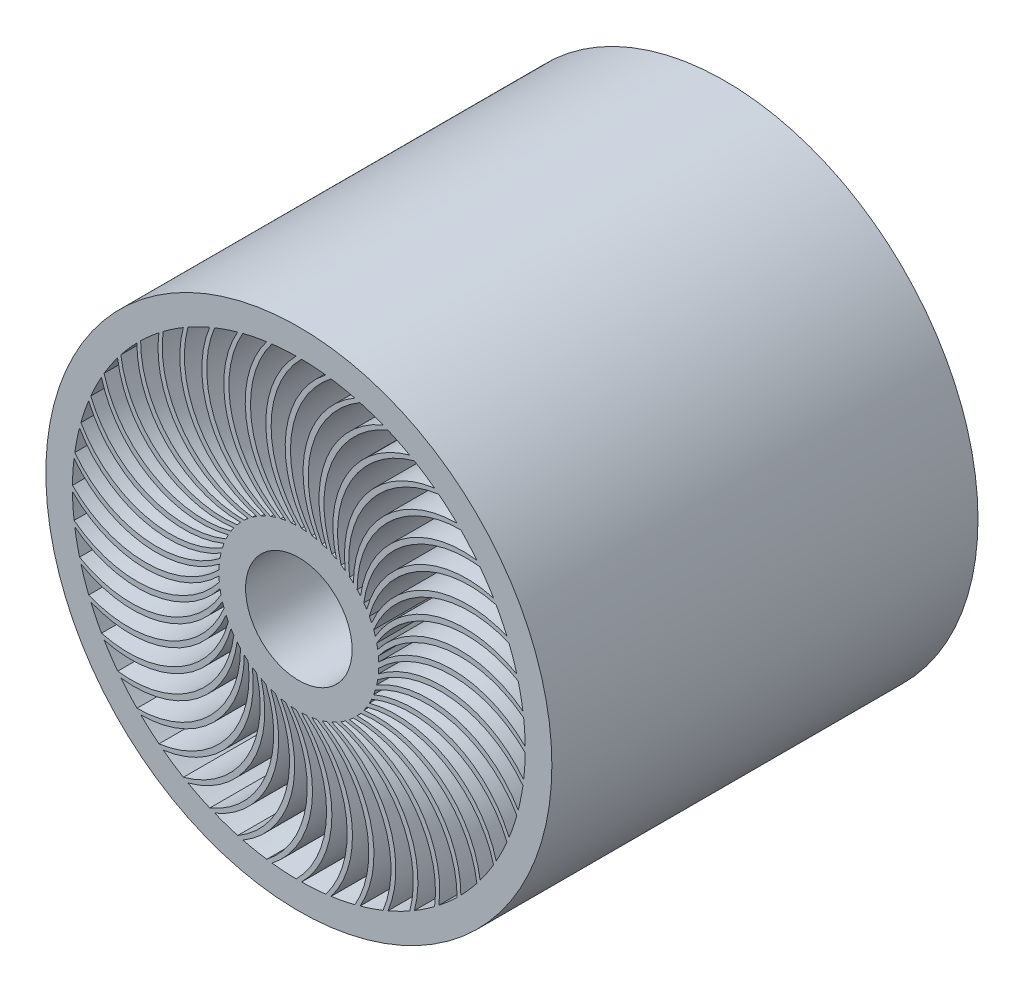
SolidWorks part; units mm, degrees
ref_plane "Front Plane" through (0, 0, 0) normal (0, 0, 1) x (1, 0, 0)
ref_plane "Top Plane" through (0, 0, 0) normal (0, 1, 0) x (1, 0, 0)
ref_plane "Right Plane" through (0, 0, 0) normal (1, 0, 0) x (0, 0, -1)
sketch "Sketch1" plane through (0, 0, 0) normal (0, 0, 1) x (1, 0, 0)
  line L0 (0, 38.1) -> (0, 107.95)
  line L1 (0, 107.95) -> (99.4973, 107.95) construction
  circle A0 centre (0, 0) radius 127
  circle A1 centre (0, 0) radius 120.65
  circle A2 centre (0, 0) radius 107.95
  circle A3 centre (0, 0) radius 25.4
  circle A4 centre (0, 0) radius 38.1
  arc A5 (0, 38.1) -> (0, 107.95) centre (34.925, 73.025) cw
  arc A6 (1.2679, 38.0789) -> (1.2468, 107.95) centre (36.1718, 73.025) cw
  arc A7 (-1.2721, 38.0788) -> (-1.2934, 107.95) centre (33.6317, 73.025) cw
  arc A8 (6.2274, 37.5876) -> (15.3264, 106.8637) centre (45.394, 67.6789) cw
  arc A9 (3.7091, 37.919) -> (12.808, 107.1953) centre (42.8756, 68.0104) cw
  arc A10 (11.0802, 36.4532) -> (29.1438, 103.949) centre (53.8395, 61.1748) cw
  arc A11 (8.6268, 37.1105) -> (26.6902, 104.6064) centre (51.3859, 61.8322) cw
  arc A12 (15.7436, 34.6951) -> (42.4626, 99.2557) centre (61.3638, 53.624) cw
  arc A13 (13.3968, 35.667) -> (40.1158, 100.2277) centre (59.0171, 54.596) cw
  arc A14 (20.1375, 32.3433) -> (55.0548, 92.864) centre (67.8382, 45.1556) cw
  arc A15 (17.9377, 33.6132) -> (52.8549, 94.1341) centre (65.6384, 46.4257) cw
  arc A16 (24.1869, 29.4382) -> (66.7049, 84.8835) centre (73.1518, 35.9146) cw
  arc A17 (22.1717, 30.9843) -> (64.6897, 86.4298) centre (71.1366, 37.461) cw
  arc A18 (27.8224, 26.0293) -> (77.2138, 75.4506) centre (77.2138, 26.0592) cw
  arc A19 (26.0262, 27.8253) -> (75.4176, 77.2467) centre (75.4176, 27.8553) cw
  arc A20 (30.9819, 22.1751) -> (86.4015, 64.7267) centre (79.9546, 15.7578) cw
  arc A21 (29.4355, 24.1901) -> (84.8552, 66.7419) centre (78.4083, 17.773) cw
  arc A22 (33.6112, 17.9414) -> (94.1108, 52.8952) centre (81.3274, 5.1868) cw
  arc A23 (32.3411, 20.141) -> (92.8408, 55.0951) centre (80.0573, 7.3866) cw
  arc A24 (35.6655, 13.4008) -> (100.2099, 40.1588) centre (81.3086, -5.4729) cw
  arc A25 (34.6934, 15.7474) -> (99.2379, 42.5056) centre (80.3366, -3.1261) cw
  arc A26 (37.1095, 8.6308) -> (104.5944, 26.7352) centre (79.8987, -16.039) cw
  arc A27 (36.452, 11.0843) -> (103.937, 29.1888) centre (79.2412, -13.5854) cw
  arc A28 (37.9186, 3.7132) -> (107.1892, 12.8542) centre (77.1216, -26.3307) cw
  arc A29 (37.5869, 6.2315) -> (106.8577, 15.3726) centre (76.7901, -23.8123) cw
  arc A30 (38.0789, -1.2679) -> (107.95, -1.2468) centre (73.025, -36.1718) cw
  arc A31 (38.0788, 1.2721) -> (107.95, 1.2934) centre (73.025, -33.6317) cw
  arc A32 (37.5876, -6.2274) -> (106.8637, -15.3264) centre (67.6789, -45.394) cw
  arc A33 (37.919, -3.7091) -> (107.1953, -12.808) centre (68.0104, -42.8756) cw
  arc A34 (36.4532, -11.0802) -> (103.949, -29.1438) centre (61.1748, -53.8395) cw
  arc A35 (37.1105, -8.6268) -> (104.6064, -26.6902) centre (61.8322, -51.3859) cw
  arc A36 (34.6951, -15.7436) -> (99.2557, -42.4626) centre (53.624, -61.3638) cw
  arc A37 (35.667, -13.3968) -> (100.2277, -40.1158) centre (54.596, -59.0171) cw
  arc A38 (32.3433, -20.1375) -> (92.864, -55.0548) centre (45.1556, -67.8382) cw
  arc A39 (33.6132, -17.9377) -> (94.1341, -52.8549) centre (46.4257, -65.6384) cw
  arc A40 (29.4382, -24.1869) -> (84.8835, -66.7049) centre (35.9146, -73.1518) cw
  arc A41 (30.9843, -22.1717) -> (86.4298, -64.6897) centre (37.461, -71.1366) cw
  arc A42 (26.0293, -27.8224) -> (75.4506, -77.2138) centre (26.0592, -77.2138) cw
  arc A43 (27.8253, -26.0262) -> (77.2467, -75.4176) centre (27.8553, -75.4176) cw
  arc A44 (22.1751, -30.9819) -> (64.7267, -86.4015) centre (15.7578, -79.9546) cw
  arc A45 (24.1901, -29.4355) -> (66.7419, -84.8552) centre (17.773, -78.4083) cw
  arc A46 (17.9414, -33.6112) -> (52.8952, -94.1108) centre (5.1868, -81.3274) cw
  arc A47 (20.141, -32.3411) -> (55.0951, -92.8408) centre (7.3866, -80.0573) cw
  arc A48 (13.4008, -35.6655) -> (40.1588, -100.2099) centre (-5.4729, -81.3086) cw
  arc A49 (15.7474, -34.6934) -> (42.5056, -99.2379) centre (-3.1261, -80.3366) cw
  arc A50 (8.6308, -37.1095) -> (26.7352, -104.5944) centre (-16.039, -79.8987) cw
  arc A51 (11.0843, -36.452) -> (29.1888, -103.937) centre (-13.5854, -79.2412) cw
  arc A52 (3.7132, -37.9186) -> (12.8542, -107.1892) centre (-26.3307, -77.1216) cw
  arc A53 (6.2315, -37.5869) -> (15.3726, -106.8577) centre (-23.8123, -76.7901) cw
  arc A54 (-1.2679, -38.0789) -> (-1.2468, -107.95) centre (-36.1718, -73.025) cw
  arc A55 (1.2721, -38.0788) -> (1.2934, -107.95) centre (-33.6317, -73.025) cw
  arc A56 (-6.2274, -37.5876) -> (-15.3264, -106.8637) centre (-45.394, -67.6789) cw
  arc A57 (-3.7091, -37.919) -> (-12.808, -107.1953) centre (-42.8756, -68.0104) cw
  arc A58 (-11.0802, -36.4532) -> (-29.1438, -103.949) centre (-53.8395, -61.1748) cw
  arc A59 (-8.6268, -37.1105) -> (-26.6902, -104.6064) centre (-51.3859, -61.8322) cw
  arc A60 (-15.7436, -34.6951) -> (-42.4626, -99.2557) centre (-61.3638, -53.624) cw
  arc A61 (-13.3968, -35.667) -> (-40.1158, -100.2277) centre (-59.0171, -54.596) cw
  arc A62 (-20.1375, -32.3433) -> (-55.0548, -92.864) centre (-67.8382, -45.1556) cw
  arc A63 (-17.9377, -33.6132) -> (-52.8549, -94.1341) centre (-65.6384, -46.4257) cw
  arc A64 (-24.1869, -29.4382) -> (-66.7049, -84.8835) centre (-73.1518, -35.9146) cw
  arc A65 (-22.1717, -30.9843) -> (-64.6897, -86.4298) centre (-71.1366, -37.461) cw
  arc A66 (-27.8224, -26.0293) -> (-77.2138, -75.4506) centre (-77.2138, -26.0592) cw
  arc A67 (-26.0262, -27.8253) -> (-75.4176, -77.2467) centre (-75.4176, -27.8553) cw
  arc A68 (-30.9819, -22.1751) -> (-86.4015, -64.7267) centre (-79.9546, -15.7578) cw
  arc A69 (-29.4355, -24.1901) -> (-84.8552, -66.7419) centre (-78.4083, -17.773) cw
  arc A70 (-33.6112, -17.9414) -> (-94.1108, -52.8952) centre (-81.3274, -5.1868) cw
  arc A71 (-32.3411, -20.141) -> (-92.8408, -55.0951) centre (-80.0573, -7.3866) cw
  arc A72 (-35.6655, -13.4008) -> (-100.2099, -40.1588) centre (-81.3086, 5.4729) cw
  arc A73 (-34.6934, -15.7474) -> (-99.2379, -42.5056) centre (-80.3366, 3.1261) cw
  arc A74 (-37.1095, -8.6308) -> (-104.5944, -26.7352) centre (-79.8987, 16.039) cw
  arc A75 (-36.452, -11.0843) -> (-103.937, -29.1888) centre (-79.2412, 13.5854) cw
  arc A76 (-37.9186, -3.7132) -> (-107.1892, -12.8542) centre (-77.1216, 26.3307) cw
  arc A77 (-37.5869, -6.2315) -> (-106.8577, -15.3726) centre (-76.7901, 23.8123) cw
  arc A78 (-38.0789, 1.2679) -> (-107.95, 1.2468) centre (-73.025, 36.1718) cw
  arc A79 (-38.0788, -1.2721) -> (-107.95, -1.2934) centre (-73.025, 33.6317) cw
  arc A80 (-37.5876, 6.2274) -> (-106.8637, 15.3264) centre (-67.6789, 45.394) cw
  arc A81 (-37.919, 3.7091) -> (-107.1953, 12.808) centre (-68.0104, 42.8756) cw
  arc A82 (-36.4532, 11.0802) -> (-103.949, 29.1438) centre (-61.1748, 53.8395) cw
  arc A83 (-37.1105, 8.6268) -> (-104.6064, 26.6902) centre (-61.8322, 51.3859) cw
  arc A84 (-34.6951, 15.7436) -> (-99.2557, 42.4626) centre (-53.624, 61.3638) cw
  arc A85 (-35.667, 13.3968) -> (-100.2277, 40.1158) centre (-54.596, 59.0171) cw
  arc A86 (-32.3433, 20.1375) -> (-92.864, 55.0548) centre (-45.1556, 67.8382) cw
  arc A87 (-33.6132, 17.9377) -> (-94.1341, 52.8549) centre (-46.4257, 65.6384) cw
  arc A88 (-29.4382, 24.1869) -> (-84.8835, 66.7049) centre (-35.9146, 73.1518) cw
  arc A89 (-30.9843, 22.1717) -> (-86.4298, 64.6897) centre (-37.461, 71.1366) cw
  arc A90 (-26.0293, 27.8224) -> (-75.4506, 77.2138) centre (-26.0592, 77.2138) cw
  arc A91 (-27.8253, 26.0262) -> (-77.2467, 75.4176) centre (-27.8553, 75.4176) cw
  arc A92 (-22.1751, 30.9819) -> (-64.7267, 86.4015) centre (-15.7578, 79.9546) cw
  arc A93 (-24.1901, 29.4355) -> (-66.7419, 84.8552) centre (-17.773, 78.4083) cw
  arc A94 (-17.9414, 33.6112) -> (-52.8952, 94.1108) centre (-5.1868, 81.3274) cw
  arc A95 (-20.141, 32.3411) -> (-55.0951, 92.8408) centre (-7.3866, 80.0573) cw
  arc A96 (-13.4008, 35.6655) -> (-40.1588, 100.2099) centre (5.4729, 81.3086) cw
  arc A97 (-15.7474, 34.6934) -> (-42.5056, 99.2379) centre (3.1261, 80.3366) cw
  arc A98 (-8.6308, 37.1095) -> (-26.7352, 104.5944) centre (16.039, 79.8987) cw
  arc A99 (-11.0843, 36.452) -> (-29.1888, 103.937) centre (13.5854, 79.2412) cw
  arc A100 (-3.7132, 37.9186) -> (-12.8542, 107.1892) centre (26.3307, 77.1216) cw
  arc A101 (-6.2315, 37.5869) -> (-15.3726, 106.8577) centre (23.8123, 76.7901) cw
  point P158 (0, 0)
  dimension "D1" = 254
  dimension "D2" = 241.3
  dimension "D3" = 215.9
  dimension "D4" = 50.8
  dimension "D5" = 76.2
  dimension "D6" = 2
  dimension "D9" = 2.54
  dimension "D7" = 2
  dimension "D8" = 48
extrude "Boss-Extrude2" add sketch "Sketch1" along normal blind 203.2 contours A4 | A79 A4 A78 A2 | A81 A4 A80 A2 | A83 A4 A82 A2 | A85 A4 A84 A2 | A87 A4 A86 A2 | A89 A4 A88 A2 | A91 A4 A90 A2 | A93 A4 A92 A2 | A95 A4 A94 A2 | A97 A4 A96 A2 | A99 A4 A98 A2 | A101 A4 A100 A2 | A4 A6 L0 | L0 A6 A5 | A7 A4 A5 A2 | L0 A6 A2 | A9 L0 A8 A2 | A9 L0 A8 | A9 A4 A8 L0 | A11 A4 A10 A2 | A13 A4 A12 A2 | A15 A4 A14 A2 | A17 A4 A16 A2 | A19 A4 A18 A2 | A21 A4 A20 A2 | A23 A4 A22 A2 | A25 A4 A24 A2 | A27 A4 A26 A2 | A29 A4 A28 A2 | A31 A4 A30 A2 | A33 A4 A32 A2 | A35 A4 A34 A2 | A37 A4 A36 A2 | A39 A4 A38 A2 | A41 A4 A40 A2 | A43 A4 A42 A2 | A45 A4 A44 A2 | A47 A4 A46 A2 | A49 A4 A48 A2 | A51 A4 A50 A2 | A53 A4 A52 A2 | A55 A4 A54 A2 | A57 A4 A56 A2 | A59 A4 A58 A2 | A61 A4 A60 A2 | A63 A4 A62 A2 | A65 A4 A64 A2 | A67 A4 A66 A2 | A69 A4 A68 A2 | A71 A4 A70 A2 | A73 A4 A72 A2 | A75 A4 A74 A2 | A77 A4 A76 A2 | A2 L1 A1 A6 | L1 A2 A6 region at (-13.7531, 73.025, 0) region at (0.4188, 38.5237, 0) region at (0.6161, 37.0172, 0) region at (-0.6373, 38.1663, 0) region at (0.4111, 107.52, 0) region at (99.7068, 61.6699, 0) region at (0.9323, 107.9479, 0) region at (-6.0211, 68.0104, 0) region at (2.3373, 41.8954, 0) region at (-5.0704, 38.497, 0) region at (6.0662, 98.5561, 0) region at (4.3808, 74.4062, 0) region at (-10.0529, 37.5098, 0) region at (14.0547, 73.1981, 0) region at (-14.8627, 35.8761, 0) region at (23.4859, 70.739, 0) region at (-19.4166, 33.6263, 0) region at (32.5153, 67.0706, 0) region at (-23.6374, 30.8013, 0) region at (40.9903, 62.254, 0) region at (-27.4543, 27.4512, 0) region at (48.7665, 56.3697, 0) region at (-30.8039, 23.634, 0) region at (55.7089, 49.5189, 0) region at (-33.6285, 19.4129, 0) region at (61.697, 41.8207, 0) region at (-35.8778, 14.8587, 0) region at (66.6281, 33.4092, 0) region at (-37.5109, 10.0488, 0) region at (70.4183, 24.4307, 0) region at (-38.4975, 5.0661, 0) region at (73.0047, 15.0406, 0) region at (-38.8192, -0.0021, 0) region at (-38.497, -5.0704, 0) region at (74.342, 5.3727, 0) region at (-37.5098, -10.0529, 0) region at (74.4062, -4.3808, 0) region at (-35.8761, -14.8627, 0) region at (73.1981, -14.0547, 0) region at (-33.6263, -19.4166, 0) region at (70.739, -23.4859, 0) region at (-30.8013, -23.6374, 0) region at (67.0706, -32.5153, 0) region at (-27.4512, -27.4543, 0) region at (62.254, -40.9903, 0) region at (-23.634, -30.8039, 0) region at (56.3697, -48.7665, 0) region at (-19.4129, -33.6285, 0) region at (49.5189, -55.7089, 0) region at (-14.8587, -35.8778, 0) region at (41.8207, -61.697, 0) region at (-10.0488, -37.5109, 0) region at (33.4092, -66.6281, 0) region at (-5.0661, -38.4975, 0) region at (24.4307, -70.4183, 0) region at (0.0021, -38.8192, 0)
ref_plane "Plane1" through (127, 0, 0) normal (1, 0, 0) x (0, 0, -1)
sketch "Sketch2" plane through (127, 0, 0) normal (1, 0, 0) x (0, 0, -1)
  line L0 (-203.2, 0) -> (0, 0)
  line L1 (-203.2, 120.65) -> (-203.2, -120.65) construction
  line L2 (-203.2, 3.175) -> (0, 3.175)
  line L3 (-203.2, -3.175) -> (0, -3.175)
  line L4 (-101.6, 0) -> (-101.6, -3.7197)
  line L5 (-101.6, -12.7) -> (-127, 12.7)
  line L6 (-203.2, -12.7) -> (0, -12.7)
  line L7 (-203.2, 12.7) -> (0, 12.7)
  line L8 (-101.6, -12.7) -> (-76.2, 12.7)
  line L9 (-101.6, -3.7197) -> (-118.0197, 12.7)
  line L10 (-101.6, -3.7197) -> (-85.1803, 12.7)
  line L11 (-97.1099, -8.2099) -> (-122.5099, 17.1901) construction
  line L12 (-106.0901, -8.2099) -> (-80.6901, 17.1901) construction
  point P24 (-80.3149, -38.5276)
  point P25 (-87.9152, -6.5316)
  dimension "D1" = 3.175
  dimension "D3" = 45
  dimension "D2" = 3.175
  dimension "D5" = 12.7
  dimension "D6" = 12.7
  dimension "D7" = 6.35
  dimension "D8" = 6.35
